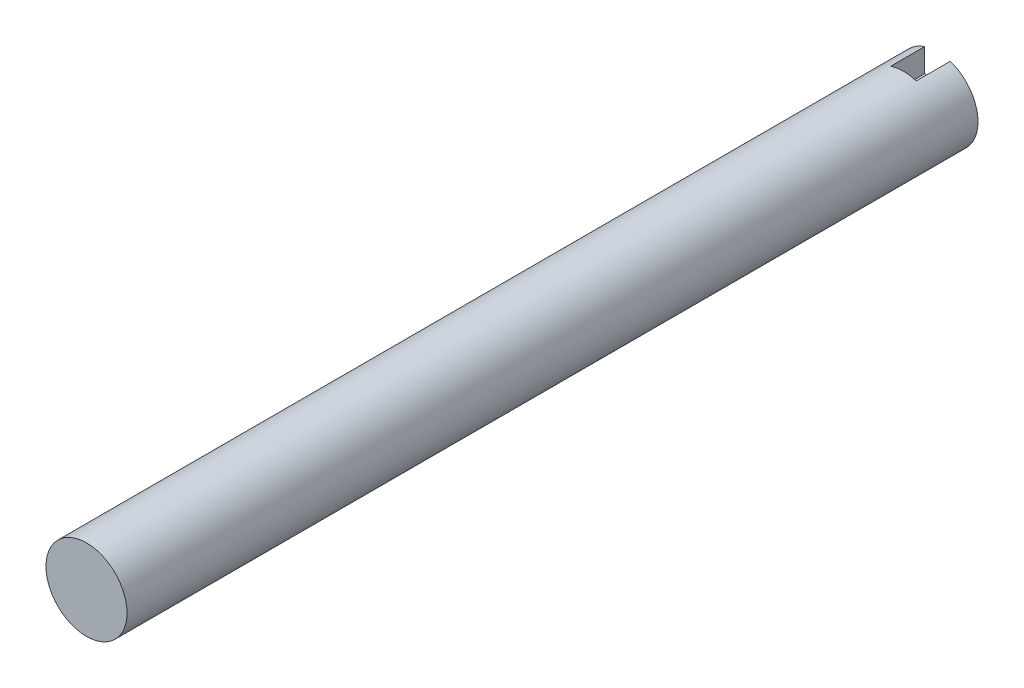
SolidWorks part; units mm, degrees
ref_plane "Front Plane" through (0, 0, 0) normal (0, 0, 1) x (1, 0, 0)
ref_plane "Top Plane" through (0, 0, 0) normal (0, 1, 0) x (1, 0, 0)
ref_plane "Right Plane" through (0, 0, 0) normal (1, 0, 0) x (0, 0, -1)
sketch "Sketch1" plane through (0, 0, 0) normal (0, 0, 1) x (1, 0, 0)
  line L1 (-1.5, 7.7625) -> (1.5, 7.7625)
  line L2 (-1.5, 7.7625) -> (-1.5, 1.7625)
  line L3 (-1.5, 1.7625) -> (1.5, 1.7625)
  line L4 (1.5, 7.7625) -> (1.5, 1.7625)
  line L5 (-1.5, 7.7625) -> (1.5, 1.7625) construction
  line L6 (-1.5, 1.7625) -> (1.5, 7.7625) construction
  circle A0 centre (0, 0) radius 4.7625
  point P3 (0, 4.7625)
  dimension "D1" = 9.525
  dimension "D2" = 3
  dimension "D3" = 3
extrude "Boss-Extrude1" add sketch "Sketch1" along normal blind 100 contours L2 A0 L4 L3 | L4 A0 L2 L3 region at (0, 3.2234, 0) region at (0, -0.4518, 0)
extrude "Cut-Extrude1" cut sketch "Sketch1<3>" along normal blind 4 contours L4 A0 L2 L3 region at (0, 3.2234, 0)
sketch "Sketch1<3>" plane through (0, 0, 0) normal (0, 0, 1) x (1, 0, 0) same geometry as "Sketch1"
